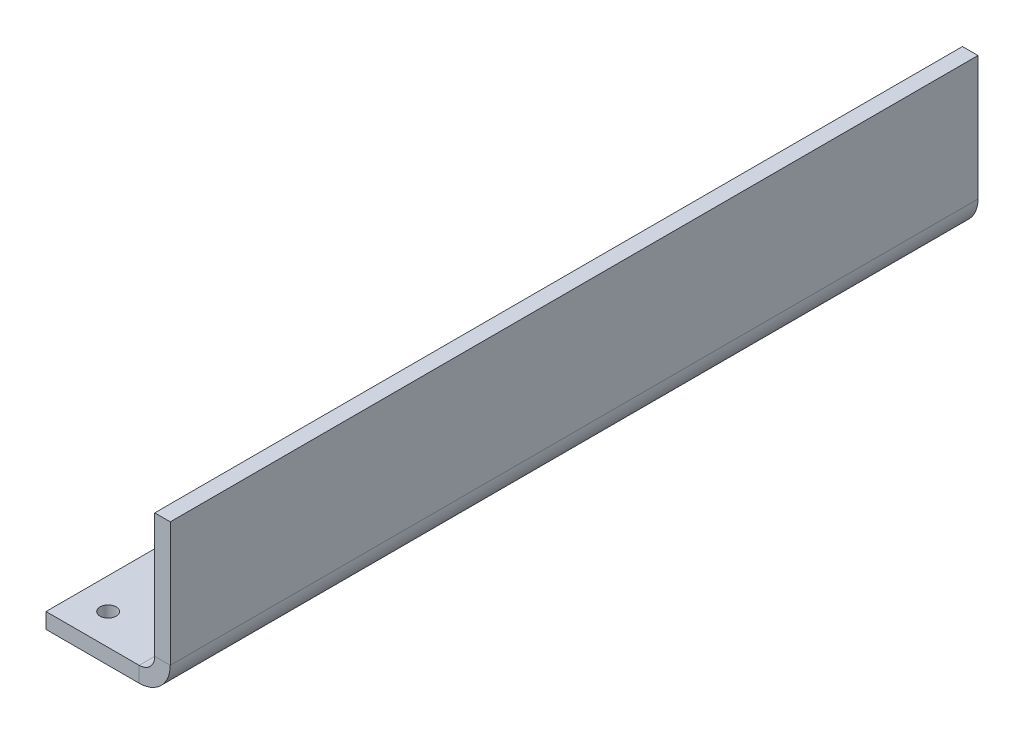
SolidWorks part; units mm, degrees
note: The reader was unsure of these and kept them because the rebuilt part matched: flange length of "Edge-Flange1".
material "6061-T6 (SS)"
ref_plane "Front" through (0, 0, 0) normal (0, 0, 1) x (1, 0, 0)
ref_plane "Top" through (0, 0, 0) normal (0, 1, 0) x (1, 0, 0)
ref_plane "Right" through (0, 0, 0) normal (1, 0, 0) x (0, 0, -1)
sketch "Sketch2" plane through (0, 0, 0) normal (1, 0, 0) x (0, 0, -1)
  line L7 (-82.55, -12.7) -> (82.55, -12.7)
  line L8 (-82.55, -12.7) -> (-82.55, 12.7)
  line L9 (-82.55, 12.7) -> (82.55, 12.7)
  line L10 (82.55, -12.7) -> (82.55, 12.7)
  line L11 (-82.55, -12.7) -> (82.55, 12.7) construction
  line L12 (-82.55, 12.7) -> (82.55, -12.7) construction
  point P0 (0, 0)
  dimension "D1" = 25.4
  dimension "D2" = 165.1
base flange "Base-Flange1" sketch "Sketch2" thickness 3.175 reverse thickness direction no parameters "D1"=3.175
edge flange "Edge-Flange1" sketch "Sketch11" flange angle 90 flange length 25.4 flange position bend outside bend radius 3.175 thickness 3.175 relief rectangular parameters "D6"=10
bend "EdgeBend2" bend radius 3.175 bend angle 90 parameters "D5"=1
sketch "Sketch11" plane through (-3.175, -12.7, 0) normal (0, -1, 0) x (0, 0, 1)
  line L1 (82.55, 0) -> (-82.55, 0) construction
  line L2 (82.55, 0) -> (82.55, 22.225)
  line L3 (82.55, 22.225) -> (-82.55, 22.225)
  line L4 (-82.55, 22.225) -> (-82.55, 0)
  line L5 (82.55, 0) -> (-82.55, 0)
sketch "Sketch14" plane through (0, -15.875, 0) normal (0, 1, 0) x (1, 0, 0)
  line L0 (-25.4, 82.55) -> (-6.35, 82.55) construction
  line L1 (-25.4, -82.55) -> (-25.4, 82.55) construction
  point P0 (-12.7, 76.2)
  point P2 (-19.05, 50.8)
  point P17 (-12.7, 12.7)
  point P18 (-19.05, -12.7)
  point P19 (-12.7, -50.8)
  point P20 (-19.05, -76.2)
  dimension "D1" = 6.35
  dimension "D2" = 25.4
  dimension "D3" = 6.35
  dimension "D4" = 12.7
  dimension "D6" = 38.1
  dimension "D5" = 3
hole_wizard "1/8 (0.13) Diameter Hole1" positions "Sketch14" profile "Sketch13" hole size "1/8" standard "ANSI Inch" end condition through all
sketch "Sketch13" plane through (-12.7, -15.875, -76.2) normal (1, 0, 0) x (0, 0, 1)
  line L0 (0, 0) -> (0, 3.175)
  line L1 (0, 3.175) -> (1.651, 3.175)
  line L2 (1.651, 3.175) -> (1.651, 0)
  line L5 (1.651, 0) -> (0, 0)
  line L11 (0, -6.35) -> (0, 107.95) construction
  dimension "Thru Hole Dia." = 3.302
  dimension "Thru Hole Depth" = 3.175
sketch "Sketch15" [suppressed] plane through (-3.175, 0, 0) normal (-1, 0, 0) x (0, 0, 1)
  line L0 (-12.7, 6.35) -> (12.7, 6.35) construction
  line L1 (-12.7, 7.9375) -> (12.7, 7.9375)
  line L2 (-12.7, 4.7625) -> (12.7, 4.7625)
  line L3 (-82.55, 12.7) -> (82.55, 12.7) construction
  arc A0 (-12.7, 7.9375) -> (-12.7, 4.7625) centre (-12.7, 6.35) ccw
  arc A1 (12.7, 4.7625) -> (12.7, 7.9375) centre (12.7, 6.35) ccw
  point P2 (0, 6.35)
  dimension "D2" = 3.175
  dimension "D1" = 25.4
  dimension "D3" = 6.35
extrude "Cut-Extrude1" [suppressed] cut sketch "Sketch15" against normal through all
sketch "Bend-Lines1" [suppressed] plane through (0, 0, 0) normal (0, 1, 0) x (1, 0, 0)
sketch "Bounding-Box1" [suppressed] plane through (0, 0, 0) normal (0, 1, 0) x (1, 0, 0)
sheet metal parameters "Sheet-Metal8" thickness 3.175 parameters "D1"=3.175
flat pattern "Flat-Pattern8" [suppressed]
sketch "Bend-Lines2" plane through (0, 0, 0) normal (0, 1, 0) x (1, 0, 0)
sketch "Bounding-Box2" [suppressed] plane through (0, 0, 0) normal (0, 1, 0) x (1, 0, 0)
sheet metal parameters "Sheet-Metal9" thickness 3.175 parameters "D1"=3.175
flat pattern "Flat-Pattern8" [suppressed]
sketch "Bend-Lines2" plane through (0, 0, 0) normal (0, 1, 0) x (1, 0, 0)
sketch "Bounding-Box2" [suppressed] plane through (0, 0, 0) normal (0, 1, 0) x (1, 0, 0)
bend of the flat pattern "Flatten-<EdgeBend2>1"
sheet metal parameters "Sheet-Metal10" thickness 3.175 parameters "D1"=3.175
flat pattern "Flat-Pattern8" [suppressed]
sketch "Bend-Lines2" plane through (0, 0, 0) normal (0, 1, 0) x (1, 0, 0)
sketch "Bounding-Box2" [suppressed] plane through (0, 0, 0) normal (0, 1, 0) x (1, 0, 0)
bend of the flat pattern "Flatten-<EdgeBend2>1"
sheet metal parameters "Sheet-Metal11" thickness 3.175 parameters "D1"=3.175
flat pattern "Flat-Pattern8" [suppressed]
sketch "Bend-Lines2" plane through (0, 0, 0) normal (0, 1, 0) x (1, 0, 0)
sketch "Bounding-Box2" [suppressed] plane through (0, 0, 0) normal (0, 1, 0) x (1, 0, 0)
bend of the flat pattern "Flatten-<EdgeBend2>1"
